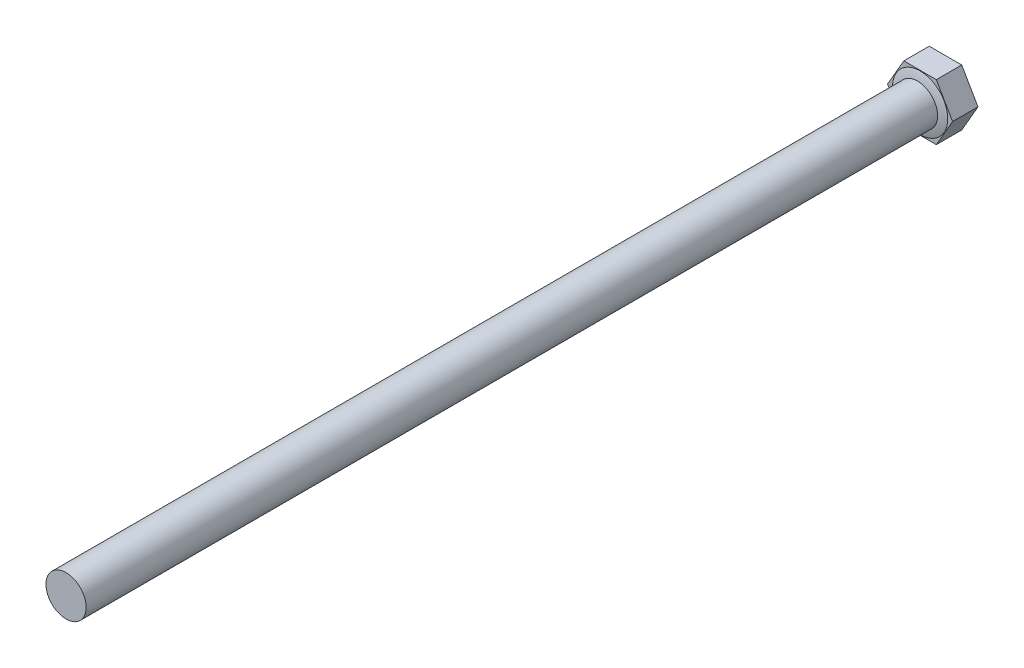
SolidWorks part; units mm, degrees
ref_plane "Front Plane" through (0, 0, 0) normal (0, 0, 1) x (1, 0, 0)
ref_plane "Top Plane" through (0, 0, 0) normal (0, 1, 0) x (1, 0, 0)
ref_plane "Right Plane" through (0, 0, 0) normal (1, 0, 0) x (0, 0, -1)
sketch "Sketch1" plane through (0, 0, 0) normal (0, 0, 1) x (1, 0, 0)
  line L1 (6.3055, 0) -> (3.1528, 5.4607)
  line L2 (3.1528, 5.4607) -> (-3.1528, 5.4607)
  line L3 (-3.1528, 5.4607) -> (-6.3055, 0)
  line L4 (-6.3055, 0) -> (-3.1528, -5.4607)
  line L5 (-3.1528, -5.4607) -> (3.1528, -5.4607)
  line L6 (3.1528, -5.4607) -> (6.3055, 0)
  circle A0 centre (0, 0) radius 5.4607 construction
extrude "Boss-Extrude1" add sketch "Sketch1" along normal blind 4.9276
sketch "Sketch2" plane through (0, 0, 4.9276) normal (0, 0, 1) x (1, 0, 0)
  circle A0 centre (0, 0) radius 5.3551
extrude "Boss-Extrude2" add sketch "Sketch2" along normal blind 0.4953
fillet "Fillet1" radius 10.16 1 edges at (5.3551, 0, 5.4229)
sketch "Sketch6" plane through (0, 0, 5.4229) normal (0, 0, 1) x (1, 0, 0)
  circle A0 centre (0, 0) radius 3.8989
  dimension "D1" = 7.7978
extrude "Boss-Extrude3" add sketch "Sketch6" along normal blind 165.1
